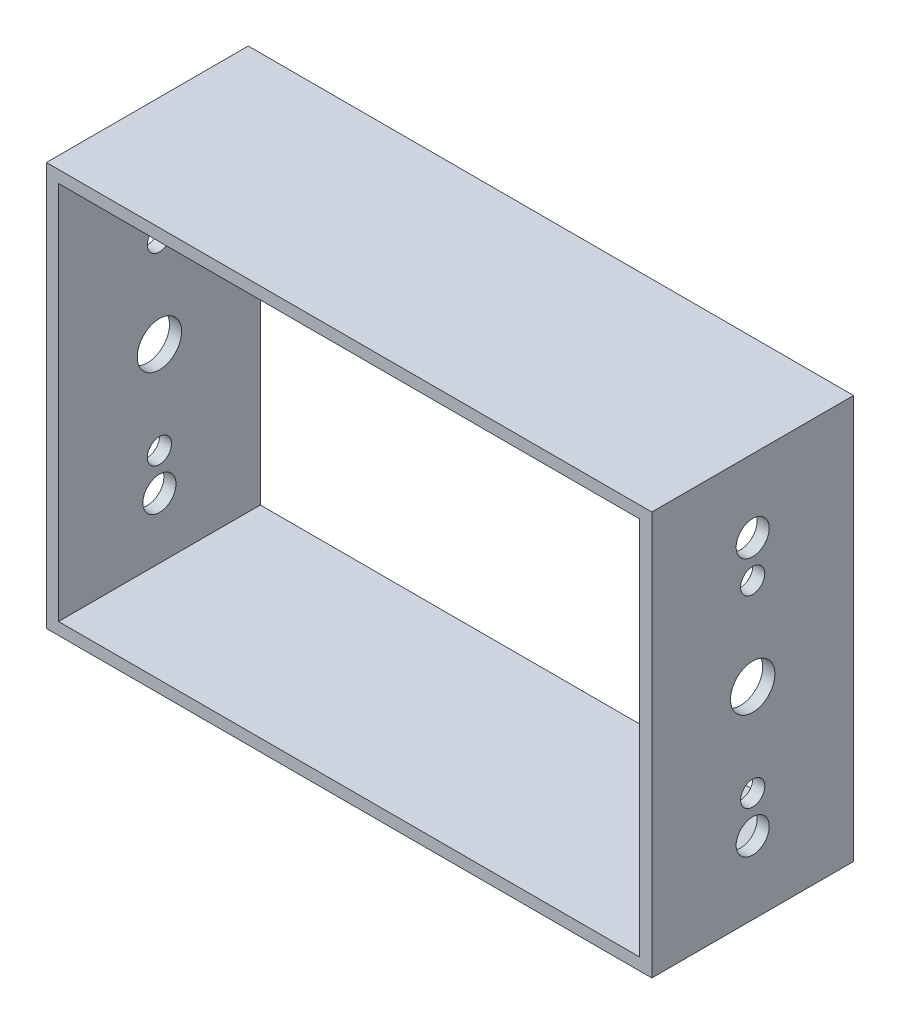
SolidWorks part; units mm, degrees
ref_plane "Front Plane" through (0, 0, 0) normal (0, 0, 1) x (1, 0, 0)
ref_plane "Top Plane" through (0, 0, 0) normal (0, 1, 0) x (1, 0, 0)
ref_plane "Right Plane" through (0, 0, 0) normal (1, 0, 0) x (0, 0, -1)
sketch "Sketch1" plane through (0, 0, 0) normal (0, 0, 1) x (1, 0, 0)
  line L1 (-75, 50) -> (75, 50)
  line L2 (-75, 50) -> (-75, -50)
  line L3 (-75, -50) -> (75, -50)
  line L4 (75, 50) -> (75, -50)
  line L5 (-75, 50) -> (75, -50) construction
  line L6 (-75, -50) -> (75, 50) construction
  line L7 (-72, 47) -> (72, 47)
  line L8 (-72, 47) -> (-72, -47)
  line L9 (-72, -47) -> (72, -47)
  line L10 (72, 47) -> (72, -47)
  line L11 (-72, 47) -> (72, -47) construction
  line L12 (-72, -47) -> (72, 47) construction
  point P0 (0, 0)
  point P6 (0, 0)
  dimension "D1" = 150
  dimension "D2" = 100
  dimension "D3" = 3
  dimension "D4" = 3
extrude "Boss-Extrude1" add sketch "Sketch1" along normal blind 50
sketch "Sketch3" plane through (75, 0, 0) normal (1, 0, 0) x (0, 0, -1)
  line L0 (-25, 50) -> (-25, -50) construction
  line L1 (-50, 50) -> (0, 50) construction
  line L2 (-50, -50) -> (0, -50) construction
  line L3 (-50, 0) -> (0, 0) construction
  line L4 (-50, -50) -> (-50, 50) construction
  circle A0 centre (-25, 0) radius 5.5
  dimension "D1" = 11
extrude "Cut-Extrude1" cut sketch "Sketch3" against normal blind 10
sketch "Sketch4" plane through (75, 0, 0) normal (1, 0, 0) x (0, 0, -1)
  line L0 (-25, 60.9718) -> (-25, -68.6379) construction
  line L1 (-135.9505, 0) -> (57.1259, 0) construction
  circle A2 centre (-25, 32) radius 4.1
  circle A3 centre (-25, -32) radius 4.1
  circle A4 centre (-25, 22.81) radius 3
  circle A5 centre (-25, -22.81) radius 3
  dimension "D1" = 8.2
  dimension "D2" = 32
  dimension "D3" = 6
  dimension "D4" = 22.81
ref_plane "Plane1" through (73.5, 0, 0) normal (-1, 0, 0) x (0, 0, 1)
mirror "Mirror3" about plane through (0, 0, 0) normal (1, 0, 0) of "Cut-Extrude1"
extrude "Cut-Extrude2" cut sketch "Sketch4" against normal through all
